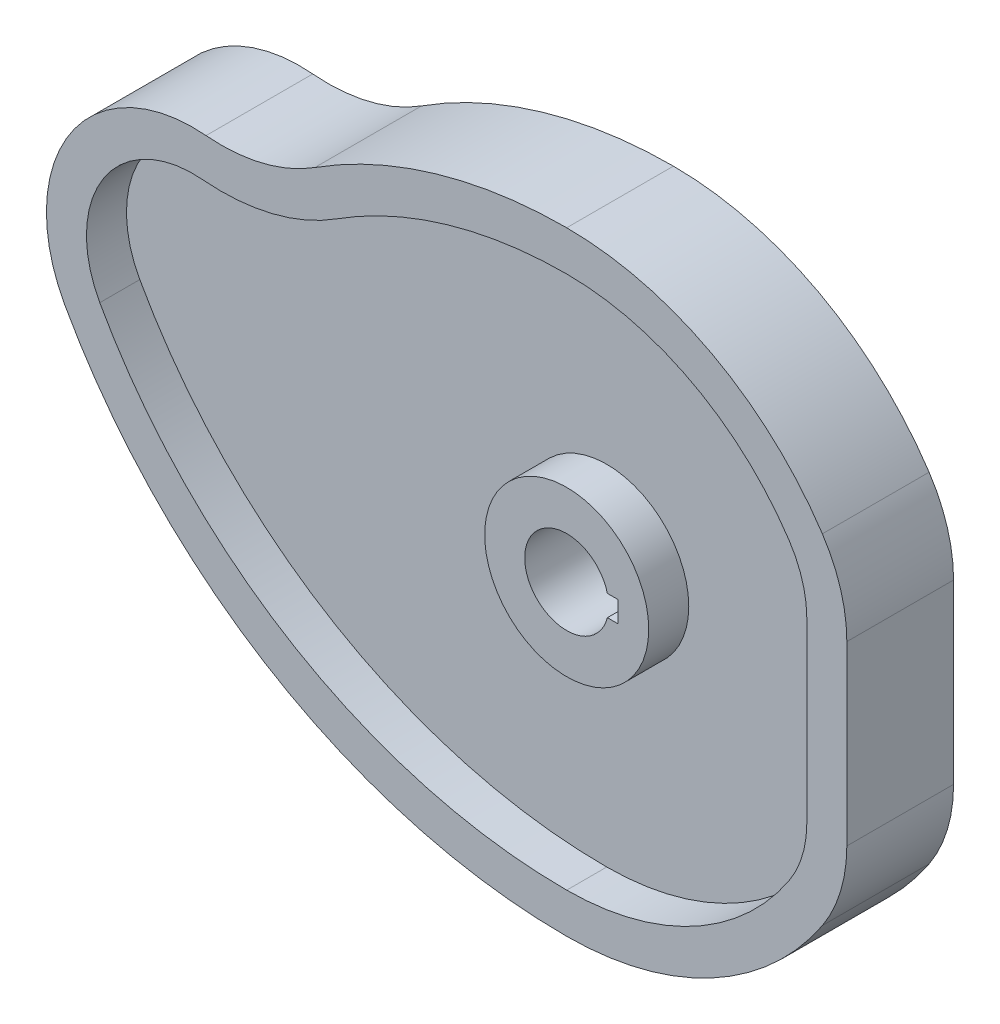
SolidWorks part; units mm, degrees
ref_plane "Front Plane" through (0, 0, 0) normal (0, 0, 1) x (1, 0, 0)
ref_plane "Top Plane" through (0, 0, 0) normal (0, 1, 0) x (1, 0, 0)
ref_plane "Right Plane" through (0, 0, 0) normal (1, 0, 0) x (0, 0, -1)
sketch "Sketch1" plane through (0, 0, 0) normal (0, 0, 1) x (1, 0, 0)
  line L0 (0, 160.0845) -> (0, -160.0845) construction
  line L1 (-264.4967, 0) -> (219.2322, 0) construction
  line L2 (114.3, 42.12) -> (114.3, -42.12)
  line L3 (133.35, 42.12) -> (133.35, -42.12)
  line L4 (-264.4967, 28.63) -> (-15.4757, 28.63) construction
  line L5 (-177.8, 114.8492) -> (-177.8, 0) construction
  line L6 (19.3649, 5) -> (24.3649, 5)
  line L7 (19.3649, -5) -> (24.3649, -5)
  line L8 (24.3649, 5) -> (24.3649, -5)
  circle A0 centre (0, 0) radius 39.05
  arc A1 (19.3649, 5) -> (19.3649, -5) centre (0, 0) ccw
  arc A2 (105.8323, 70.2035) -> (0, 127) centre (0, 0) ccw
  arc A3 (114.3, 42.12) -> (105.8323, 70.2035) centre (63.4962, 42.12) ccw
  arc A4 (114.3, -42.12) -> (105.8323, -70.2035) centre (63.4962, -42.12) cw
  arc A5 (-173.3438, 79.2342) -> (-222.2508, 4.038) centre (-177.8, 28.63) ccw
  arc A6 (0, 127) -> (-109.6209, 94.895) centre (0, -76.2) ccw
  arc A7 (-173.3438, 79.2342) -> (-109.6209, 94.895) centre (-164.4313, 180.4425) ccw
  arc A9 (0, -127) -> (105.8323, -70.2035) centre (0, 0) ccw
  arc A10 (0, -127) -> (-222.2508, 4.038) centre (0, 126.9965) cw
  arc A11 (0, 146.05) -> (-119.8978, 110.9352) centre (0, -76.2) ccw
  arc A12 (-171.6727, 98.2107) -> (-119.8978, 110.9352) centre (-164.4313, 180.4425) ccw
  arc A13 (-171.6727, 98.2107) -> (-238.9198, -5.1841) centre (-177.8, 28.63) ccw
  arc A14 (0, -146.05) -> (-238.9198, -5.1841) centre (0, 126.9965) cw
  arc A15 (0, -146.05) -> (121.7071, -80.734) centre (0, 0) ccw
  arc A16 (133.35, -42.12) -> (121.7071, -80.734) centre (63.4962, -42.12) cw
  arc A17 (133.35, 42.12) -> (121.7071, 80.734) centre (63.4962, 42.12) ccw
  arc A18 (121.7071, 80.734) -> (0, 146.05) centre (0, 0) ccw
  point P5 (0, 0)
  point P10 (114.3, 0)
  point P21 (-177.8, 28.63)
  point P29 (0, -76.2)
  point P51 (0, 0)
  dimension "D1" = 40
  dimension "D2" = 78.1
  dimension "D3" = 127
  dimension "D6" = 28.63
  dimension "D8" = 50.8
  dimension "D9" = 10
  dimension "D10" = 203.2
  dimension "D11" = 101.6
  dimension "D12" = 5
  dimension "D4" = 84.24
  dimension "D5" = 114.3
  dimension "D7" = 177.8
  dimension "D13" = 19.05
extrude "Boss-Extrude1" add sketch "Sketch1" along normal mid plane 50.8 contours A17 A18 A11 A12 A13 A14 A15 A16 L3 A9 A10 A5 A7 A6 A2 A3 L2 A4 | A0 A1 L6 L8 L7 region at (128.5491, 0, 0) region at (-37.9455, 0, 0)
extrude "Boss-Extrude2" add sketch "Sketch1<3>" along normal mid plane 12.7 contours A10 A9 A4 L2 A3 A2 A6 A7 A5 A0 region at (-42.7416, 1.2571, 0)
sketch "Sketch1<3>" plane through (0, 0, 0) normal (0, 0, 1) x (1, 0, 0) same geometry as "Sketch1"
